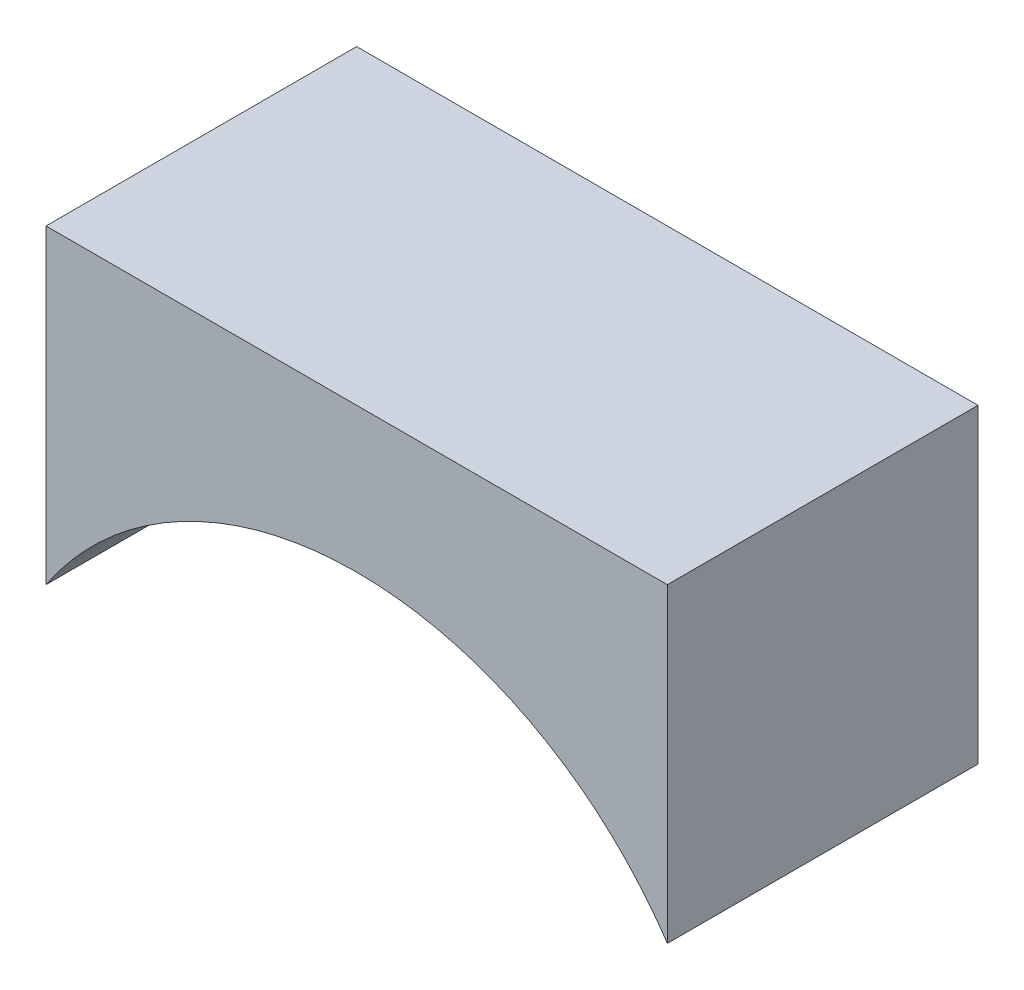
SolidWorks part; units mm, degrees
material "Silicon"
ref_plane "Front Plane" through (0, 0, 0) normal (0, 0, 1) x (1, 0, 0)
ref_plane "Top Plane" through (0, 0, 0) normal (0, 1, 0) x (1, 0, 0)
ref_plane "Right Plane" through (0, 0, 0) normal (1, 0, 0) x (0, 0, -1)
sketch "Sketch1" plane through (0, 0, 0) normal (0, 0, 1) x (1, 0, 0)
  line L2 (1400.1305, -323.2791) -> (1400.1305, -173.2791)
  line L3 (1400.1305, -173.2791) -> (1700.1305, -173.2791)
  line L4 (1700.1305, -323.2791) -> (1700.1305, -173.2791)
  spline S0 degree 3 poles (1489.7865, -594.5549) (1524.3401, -603.0384) (1559.8848, -604.6178) (1595.0546, -599.2324) (1628.4981, -587.0893) (1658.9299, -568.6549) (1685.1806, -544.6378) (1706.2414, -515.961) (1721.303, -483.7263) (1729.7865, -449.1728) (1731.3659, -413.628) (1725.9806, -378.4582) (1713.8374, -345.0147) (1695.403, -314.5829) (1671.386, -288.3322) (1642.7091, -267.2714) (1610.4745, -252.2098) (1575.9209, -243.7263) (1540.3762, -242.1469) (1505.2063, -247.5322) (1471.7629, -259.6754) (1441.3311, -278.1098) (1415.0803, -302.1268) (1394.0195, -330.8037) (1378.9579, -363.0383) (1370.4744, -397.5919) (1368.895, -433.1366) (1374.2804, -468.3065) (1386.4236, -501.7499) (1404.8579, -532.1818) (1428.875, -558.4325) (1457.5518, -579.4933) (1489.7865, -594.5549) (1524.3401, -603.0384) (1559.8848, -604.6178) knots -0.589049 -0.392699 -0.19635 0 0.19635 0.392699 0.589049 0.785398 0.981748 1.178097 1.374447 1.570796 1.767146 1.963495 2.159845 2.356194 2.552544 2.748894 2.945243 3.141593 3.337942 3.534292 3.730641 3.926991 4.12334 4.31969 4.516039 4.712389 4.908739 5.105088 5.301438 5.497787 5.694137 5.890486 6.086836 6.283185 6.479535 6.675884 6.872234 only from (1524.5052, -601.8877) to (1524.5052, -601.8877) construction
  spline S1 degree 3 poles (1700.1305, -323.2791) (1698.3174, -320.5621) (1689.6129, -308.2543) (1671.386, -288.3322) (1642.7091, -267.2714) (1610.4745, -252.2098) (1575.9209, -243.7263) (1540.3762, -242.1469) (1505.2063, -247.5322) (1471.7629, -259.6754) (1441.3311, -278.1098) (1417.4511, -299.9578) (1404.9075, -316.1219) (1400.1305, -323.2791) knots 2.301855 2.301855 2.301855 2.301855 2.356194 2.552544 2.748894 2.945243 3.141593 3.337942 3.534292 3.730641 3.926991 4.12334 4.26649 4.26649 4.26649 4.26649
  point P5 (0, 0)
  point P6 (0, 0)
  dimension "D1" = 150
  dimension "D2" = 300
extrude "Boss-Extrude1" add sketch "Sketch1" against normal blind 150
